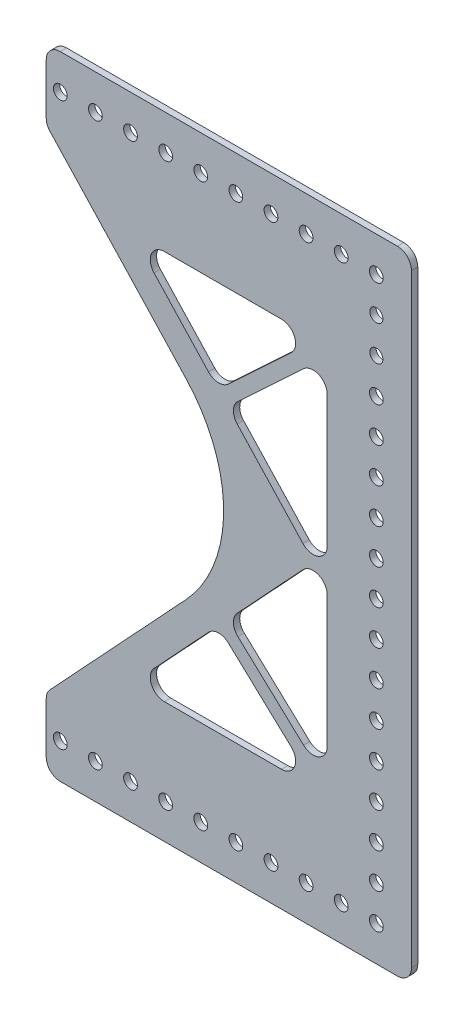
SolidWorks part; units mm, degrees
ref_plane "Front Plane" through (0, 0, 0) normal (0, 0, 1) x (1, 0, 0)
ref_plane "Top Plane" through (0, 0, 0) normal (0, 1, 0) x (1, 0, 0)
ref_plane "Right Plane" through (0, 0, 0) normal (1, 0, 0) x (0, 0, -1)
sketch "Sketch1" plane through (0, 0, 0) normal (0, 0, 1) x (1, 0, 0)
  line L0 (238.8067, 781.2872) -> (222.2967, 781.2872)
  line L4 (176.5767, 781.2872) -> (116.8867, 781.2872)
  line L5 (113.1687, 754.4243) -> (162.3479, 701.6037)
  line L6 (243.8867, 776.2072) -> (243.8867, 666.9872)
  line L7 (111.8067, 757.8859) -> (111.8067, 776.2072)
  line L8 (150.787, 728.9305) -> (170.4738, 707.786)
  line L9 (213.4067, 674.5852) -> (213.4067, 722.2064)
  line L10 (196.902, 737.4722) -> (154.5049, 737.4722)
  line L11 (243.8867, 557.7672) -> (243.8867, 666.9872)
  line L12 (238.8067, 552.6872) -> (222.2967, 552.6872)
  line L16 (113.1687, 579.55) -> (162.3479, 632.3706)
  line L17 (176.5767, 552.6872) -> (116.8867, 552.6872)
  line L18 (111.8067, 576.0884) -> (111.8067, 557.7672)
  line L19 (200.3636, 728.6742) -> (177.6534, 707.5296)
  line L20 (180.8588, 637.3423) -> (204.6087, 662.8508)
  line L21 (204.8651, 725.9243) -> (181.1151, 703.8117)
  line L22 (180.8588, 696.632) -> (204.6087, 671.1235)
  line L23 (213.4067, 659.3892) -> (213.4067, 611.768)
  line L24 (204.8651, 608.05) -> (181.1151, 630.1627)
  line L25 (200.3636, 605.3001) -> (177.6534, 626.4447)
  line L26 (150.787, 605.0438) -> (170.4738, 626.1884)
  line L27 (196.902, 596.5022) -> (154.5049, 596.5022)
  line L28 (222.2967, 552.6872) -> (176.5767, 552.6872)
  line L29 (222.2967, 781.2872) -> (176.5767, 781.2872)
  arc A0 (238.8067, 781.2872) -> (243.8867, 776.2072) centre (238.8067, 776.2072) cw
  arc A5 (116.8867, 781.2872) -> (111.8067, 776.2072) centre (116.8867, 776.2072) ccw
  circle A6 centre (142.2867, 768.5872) radius 2.4892
  circle A7 centre (154.9867, 768.5872) radius 2.4892
  circle A8 centre (167.6867, 768.5872) radius 2.4892
  circle A9 centre (231.1867, 743.1872) radius 2.3719
  circle A10 centre (231.1867, 730.4872) radius 2.4892
  circle A11 centre (231.1867, 717.7872) radius 2.4892
  circle A12 centre (231.1867, 705.0872) radius 2.4892
  circle A13 centre (231.1867, 692.3872) radius 2.4892
  arc A14 (113.1687, 754.4243) -> (111.8067, 757.8859) centre (116.8867, 757.8859) cw
  arc A15 (204.6087, 671.1235) -> (213.4067, 674.5852) centre (208.3267, 674.5852) ccw
  arc A16 (150.787, 728.9305) -> (154.5049, 737.4722) centre (154.5049, 732.3922) cw
  arc A17 (238.8067, 552.6872) -> (243.8867, 557.7672) centre (238.8067, 557.7672) ccw
  circle A22 centre (167.6867, 565.3872) radius 2.4892
  circle A23 centre (154.9867, 565.3872) radius 2.4892
  circle A24 centre (142.2867, 565.3872) radius 2.4892
  arc A25 (113.1687, 579.55) -> (111.8067, 576.0884) centre (116.8867, 576.0884) ccw
  arc A26 (116.8867, 552.6872) -> (111.8067, 557.7672) centre (116.8867, 557.7672) cw
  circle A27 centre (231.1867, 616.1872) radius 2.4892
  circle A28 centre (231.1867, 603.4872) radius 2.4892
  circle A29 centre (231.1867, 590.7872) radius 2.4892
  circle A30 centre (231.1867, 565.3872) radius 2.4892
  circle A31 centre (231.1867, 768.5872) radius 2.4892
  arc A32 (162.3479, 701.6037) -> (162.3479, 632.3706) centre (125.1681, 666.9872) cw
  circle A33 centre (231.1867, 654.2872) radius 2.4892
  circle A34 centre (231.1867, 641.5872) radius 2.4892
  circle A35 centre (231.1867, 628.8872) radius 2.4892
  circle A36 centre (116.8867, 768.5872) radius 2.4892
  circle A37 centre (129.5867, 768.5872) radius 2.4892
  circle A38 centre (129.5867, 565.3872) radius 2.4892
  circle A39 centre (116.8867, 565.3872) radius 2.4892
  arc A40 (181.1151, 703.8117) -> (180.8588, 696.632) centre (184.5767, 700.0937) ccw
  arc A41 (204.8651, 725.9243) -> (213.4067, 722.2064) centre (208.3267, 722.2064) cw
  arc A42 (200.3636, 728.6742) -> (196.902, 737.4722) centre (196.902, 732.3922) ccw
  arc A43 (177.6534, 707.5296) -> (170.4738, 707.786) centre (174.1918, 711.2476) cw
  arc A44 (204.6087, 662.8508) -> (213.4067, 659.3892) centre (208.3267, 659.3892) cw
  arc A45 (181.1151, 630.1627) -> (180.8588, 637.3423) centre (184.5767, 633.8806) cw
  arc A46 (204.8651, 608.05) -> (213.4067, 611.768) centre (208.3267, 611.768) ccw
  arc A47 (200.3636, 605.3001) -> (196.902, 596.5022) centre (196.902, 601.5822) cw
  arc A48 (177.6534, 626.4447) -> (170.4738, 626.1884) centre (174.1918, 622.7267) ccw
  arc A49 (150.787, 605.0438) -> (154.5049, 596.5022) centre (154.5049, 601.5822) ccw
  circle A50 centre (231.1867, 679.6872) radius 2.4892
  circle A51 centre (231.1867, 666.9872) radius 2.4892
  circle A52 centre (231.1867, 755.8872) radius 2.3719
  circle A53 centre (231.1867, 578.0872) radius 2.4892
  circle A54 centre (180.3867, 565.3872) radius 2.4892
  circle A55 centre (193.0867, 565.3872) radius 2.4892
  circle A56 centre (205.7867, 565.3872) radius 2.4892
  circle A57 centre (218.4867, 565.3872) radius 2.4892
  circle A58 centre (180.3867, 768.5872) radius 2.4892
  circle A59 centre (193.0867, 768.5872) radius 2.4892
  circle A60 centre (205.7867, 768.5872) radius 2.4892
  circle A61 centre (218.4867, 768.5872) radius 2.4892
  point P14 (243.8867, 666.9872)
  point P17 (218.4867, 666.9872)
  dimension "D1" = 5
  dimension "D2" = 5
extrude "Boss-Extrude1" add sketch "Sketch1" along normal blind 2.286
sketch "Sketch2" [suppressed] plane through (0, 0, 2.286) normal (0, 0, 1) x (1, 0, 0)
  line L1 (243.8867, 666.9872) -> (166.9629, 666.9872) construction
  line L2 (243.8867, 557.7672) -> (243.8867, 776.2072) construction
  circle A0 centre (164.6497, 729.7313) radius 2.54
  circle A1 centre (181.8544, 724.0904) radius 2.54
  circle A2 centre (198.8305, 691.9777) radius 2.54
  circle A3 centre (204.3595, 709.5031) radius 2.54
  circle A5 centre (198.8305, 641.9966) radius 2.54
  circle A6 centre (204.3595, 624.4712) radius 2.54
  circle A7 centre (181.8544, 609.8839) radius 2.54
  circle A8 centre (164.6497, 604.243) radius 2.54
  point P16 (204.3595, 709.5031)
  dimension "D1" = 5.08
